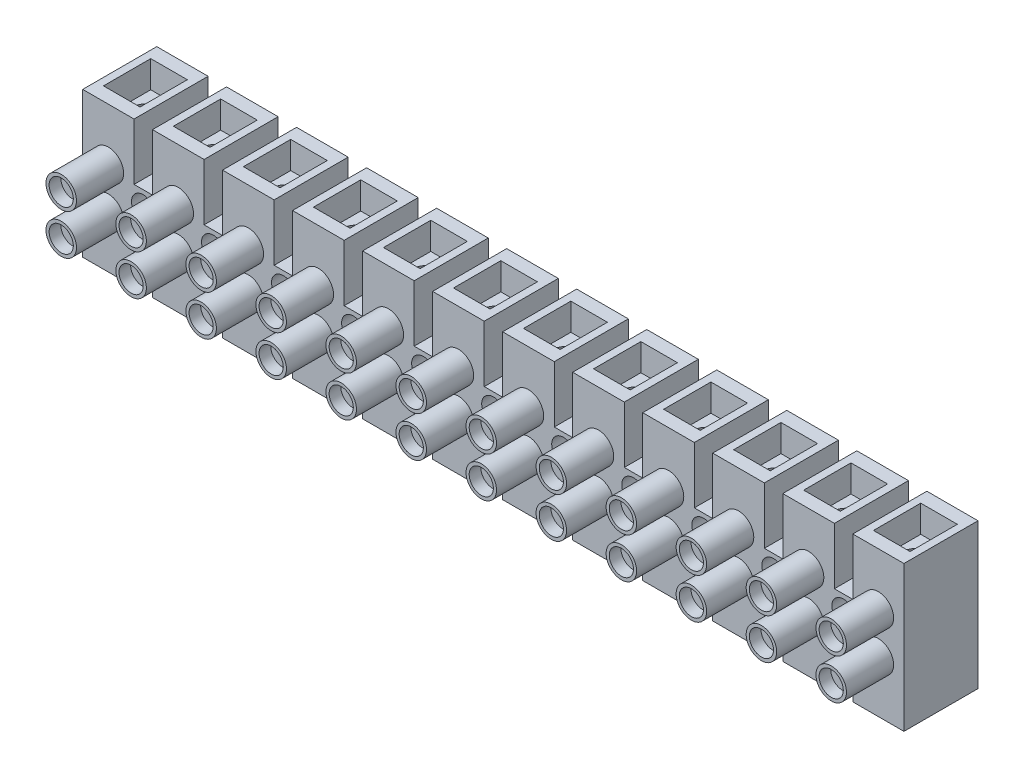
SolidWorks part; units mm, degrees
ref_plane "Front Plane" through (0, 0, 0) normal (0, 0, 1) x (1, 0, 0)
ref_plane "Top Plane" through (0, 0, 0) normal (0, 1, 0) x (1, 0, 0)
ref_plane "Right Plane" through (0, 0, 0) normal (1, 0, 0) x (0, 0, -1)
sketch "Sketch1" plane through (0, 0, 0) normal (0, 0, 1) x (1, 0, 0)
  line L1 (0, 16.9545) -> (95.758, 16.9545)
  line L2 (0, 16.9545) -> (0, 0)
  line L3 (0, 0) -> (95.758, 0)
  line L4 (95.758, 16.9545) -> (95.758, 0)
  dimension "D1" = 95.758
  dimension "D2" = 16.9545
extrude "Boss-Extrude1" add sketch "Sketch1" along normal blind 8.636
sketch "Sketch2" plane through (0, 0, 8.636) normal (0, 0, 1) x (1, 0, 0)
  line L0 (0, 8.4773) -> (95.758, 8.4773) construction
  line L1 (0, 16.9545) -> (0, 0) construction
  line L2 (95.758, 0) -> (95.758, 16.9545) construction
  line L3 (22.3202, 16.9545) -> (24.4666, 16.9545)
  line L4 (5.988, 16.9545) -> (8.1343, 16.9545)
  line L5 (5.988, 16.9545) -> (5.9881, 10.3505)
  line L6 (5.9881, 10.3505) -> (8.1343, 10.3505)
  line L7 (8.1343, 16.9545) -> (8.1343, 10.3505)
  line L8 (14.1542, 16.9545) -> (16.3005, 16.9545)
  line L9 (95.758, 16.9545) -> (0, 16.9545) construction
  line L10 (7.0612, 16.9545) -> (7.0612, 0) construction
  line L11 (15.2273, 16.9545) -> (15.2273, 0) construction
  line L12 (23.3934, 16.9545) -> (23.3934, 0) construction
  line L13 (31.5595, 16.9545) -> (31.5595, 0) construction
  line L14 (39.7256, 16.9545) -> (39.7256, 0) construction
  line L15 (47.8917, 16.9545) -> (47.8917, 0) construction
  line L16 (56.0578, 16.9545) -> (56.0578, 0) construction
  line L17 (64.2239, 16.9545) -> (64.2239, 0) construction
  line L18 (72.39, 16.9545) -> (72.39, 0) construction
  line L19 (88.7222, 16.9545) -> (88.7222, 0) construction
  line L20 (80.5561, 16.9545) -> (80.5561, 0) construction
  line L21 (0, 0) -> (95.758, 0) construction
  line L22 (14.1542, 16.9545) -> (14.1542, 10.3505)
  line L23 (14.1542, 10.3505) -> (16.3005, 10.3505)
  line L24 (16.3005, 16.9545) -> (16.3005, 10.3505)
  line L25 (22.3202, 16.9545) -> (22.3203, 10.3505)
  line L26 (22.3203, 10.3505) -> (24.4666, 10.3505)
  line L27 (24.4666, 16.9545) -> (24.4666, 10.3505)
  line L28 (30.4864, 16.9545) -> (32.6326, 16.9545)
  line L29 (30.4864, 16.9545) -> (30.4864, 10.3505)
  line L30 (30.4864, 10.3505) -> (32.6327, 10.3505)
  line L31 (32.6326, 16.9545) -> (32.6327, 10.3505)
  line L32 (38.6525, 16.9545) -> (40.7988, 16.9545)
  line L33 (38.6525, 16.9545) -> (38.6525, 10.3505)
  line L34 (38.6525, 10.3505) -> (40.7988, 10.3505)
  line L35 (40.7988, 16.9545) -> (40.7988, 10.3505)
  line L36 (46.8186, 16.9545) -> (48.9648, 16.9545)
  line L37 (46.8186, 16.9545) -> (46.8186, 10.3505)
  line L38 (46.8186, 10.3505) -> (48.9649, 10.3505)
  line L39 (48.9648, 16.9545) -> (48.9649, 10.3505)
  line L40 (54.9847, 16.9545) -> (57.131, 16.9545)
  line L41 (54.9847, 16.9545) -> (54.9847, 10.3505)
  line L42 (54.9847, 10.3505) -> (57.131, 10.3505)
  line L43 (57.131, 16.9545) -> (57.131, 10.3505)
  line L44 (63.1508, 16.9545) -> (65.2971, 16.9545)
  line L45 (63.1508, 16.9545) -> (63.1508, 10.3505)
  line L46 (63.1508, 10.3505) -> (65.2971, 10.3505)
  line L47 (65.2971, 16.9545) -> (65.2971, 10.3505)
  line L48 (71.3169, 16.9545) -> (73.4631, 16.9545)
  line L49 (71.3169, 16.9545) -> (71.3169, 10.3505)
  line L50 (71.3169, 10.3505) -> (73.4631, 10.3505)
  line L51 (73.4631, 16.9545) -> (73.4631, 10.3505)
  line L52 (79.483, 16.9545) -> (81.6292, 16.9545)
  line L53 (79.483, 16.9545) -> (79.483, 10.3505)
  line L54 (79.483, 10.3505) -> (81.6293, 10.3505)
  line L55 (81.6292, 16.9545) -> (81.6293, 10.3505)
  line L56 (87.6491, 16.9545) -> (89.7953, 16.9545)
  line L57 (87.6491, 16.9545) -> (87.6491, 10.3505)
  line L58 (87.6491, 10.3505) -> (89.7953, 10.3505)
  line L59 (89.7953, 16.9545) -> (89.7953, 10.3505)
  line L60 (5.988, 6.604) -> (8.1343, 6.604)
  line L61 (5.988, 6.604) -> (5.9881, 0)
  line L62 (5.9881, 0) -> (8.1343, 0)
  line L63 (8.1343, 6.604) -> (8.1343, 0)
  line L64 (14.1542, 6.604) -> (16.3005, 6.604)
  line L65 (14.1542, 6.604) -> (14.1542, 0)
  line L66 (14.1542, 0) -> (16.3005, 0)
  line L67 (16.3005, 6.604) -> (16.3005, 0)
  line L68 (22.3203, 6.604) -> (24.4666, 6.604)
  line L69 (22.3203, 6.604) -> (22.3203, 0)
  line L70 (22.3203, 0) -> (24.4666, 0)
  line L71 (24.4666, 6.604) -> (24.4666, 0)
  line L72 (30.4864, 6.604) -> (32.6326, 6.604)
  line L73 (30.4864, 6.604) -> (30.4864, 0)
  line L74 (30.4864, 0) -> (32.6326, 0)
  line L75 (32.6326, 6.604) -> (32.6326, 0)
  line L76 (38.6525, 6.604) -> (40.7987, 6.604)
  line L77 (38.6525, 6.604) -> (38.6525, 0)
  line L78 (38.6525, 0) -> (40.7987, 0)
  line L79 (40.7987, 6.604) -> (40.7987, 0)
  line L80 (48.9649, 6.604) -> (46.8186, 6.604)
  line L81 (48.9649, 6.604) -> (48.9649, 0)
  line L82 (48.9649, 0) -> (46.8186, 0)
  line L83 (46.8186, 6.604) -> (46.8186, 0)
  line L84 (57.131, 6.604) -> (54.9847, 6.604)
  line L85 (57.131, 6.604) -> (57.131, 0)
  line L86 (57.131, 0) -> (54.9847, 0)
  line L87 (54.9847, 6.604) -> (54.9847, 0)
  line L88 (63.1508, 6.604) -> (65.2971, 6.604)
  line L89 (63.1508, 6.604) -> (63.1508, 0)
  line L90 (63.1508, 0) -> (65.2971, 0)
  line L91 (65.2971, 6.604) -> (65.2971, 0)
  line L92 (71.3169, 6.604) -> (73.4631, 6.604)
  line L93 (71.3169, 6.604) -> (71.3169, 0)
  line L94 (71.3169, 0) -> (73.4632, 0)
  line L95 (73.4631, 6.604) -> (73.4632, 0)
  line L96 (79.483, 6.604) -> (81.6292, 6.604)
  line L97 (79.483, 6.604) -> (79.483, 0)
  line L98 (79.483, 0) -> (81.6293, 0)
  line L99 (81.6292, 6.604) -> (81.6293, 0)
  line L100 (89.7953, 6.604) -> (87.6491, 6.604)
  line L101 (89.7953, 6.604) -> (89.7953, 0)
  line L102 (89.7953, 0) -> (87.6491, 0)
  line L103 (87.6491, 6.604) -> (87.6491, 0)
  circle A0 centre (15.2273, 8.4773) radius 1.3716
  circle A1 centre (23.3934, 8.4773) radius 1.3716
  circle A2 centre (31.5595, 8.4773) radius 1.3716
  circle A3 centre (39.7256, 8.4773) radius 1.3716
  circle A4 centre (47.8917, 8.4773) radius 1.3716
  circle A5 centre (56.0578, 8.4773) radius 1.3716
  circle A6 centre (7.0612, 8.4773) radius 1.3716
  circle A7 centre (64.2239, 8.4773) radius 1.3716
  circle A8 centre (72.39, 8.4773) radius 1.3716
  circle A9 centre (80.5561, 8.4773) radius 1.3716
  circle A10 centre (88.7222, 8.4773) radius 1.3716
  dimension "D1" = 2.7432
  dimension "D2" = 7.0358
  dimension "D3" = 8.1661
  dimension "D4" = 8.1661
  dimension "D5" = 8.1661
  dimension "D6" = 8.1661
  dimension "D7" = 8.1661
  dimension "D8" = 8.1661
  dimension "D9" = 8.1661
  dimension "D10" = 8.1661
  dimension "D11" = 8.1661
  dimension "D12" = 8.1661
  dimension "D13" = 2.1463
  dimension "D14" = 6.604
extrude "Cut-Extrude2" cut sketch "Sketch2" against normal up to surface (8.636 mm away) up to face at (47.879, 8.4773, 0)
sketch "Sketch3" plane through (0, 0, 8.636) normal (0, 0, 1) x (1, 0, 0)
  line L0 (0, 6.1087) -> (95.758, 6.1087) construction
  line L1 (79.483, 16.9545) -> (73.4631, 16.9545) construction
  line L2 (0, 16.9545) -> (0, 0) construction
  line L3 (95.758, 0) -> (95.758, 16.9545) construction
  line L4 (95.758, 10.8458) -> (0, 10.8458) construction
  line L5 (47.879, 10.8458) -> (47.879, 6.1087) construction
  line L6 (95.758, 8.4773) -> (0, 8.4773) construction
  line L7 (92.7767, 16.9545) -> (92.7767, 0) construction
  line L8 (84.6392, 16.9545) -> (84.6392, 0) construction
  line L9 (76.4731, 16.9545) -> (76.4731, 0) construction
  line L10 (68.307, 16.9545) -> (68.307, 0) construction
  line L11 (60.1409, 16.9545) -> (60.1409, 0) construction
  line L12 (51.9748, 16.9545) -> (51.9748, 0) construction
  line L13 (43.8087, 16.9545) -> (43.8087, 0) construction
  line L14 (35.6425, 16.9545) -> (35.6425, 0) construction
  line L15 (27.4765, 16.9545) -> (27.4765, 0) construction
  line L16 (19.3103, 16.9545) -> (19.3104, 0) construction
  line L17 (11.1442, 16.9545) -> (11.1443, 0) construction
  line L18 (2.994, 16.9545) -> (2.994, 0) construction
  line L19 (5.988, 16.9545) -> (0, 16.9545) construction
  line L20 (0, 0) -> (5.9881, 0) construction
  line L21 (14.1542, 16.9545) -> (8.1343, 16.9545) construction
  line L22 (8.1343, 0) -> (14.1542, 0) construction
  line L23 (22.3202, 16.9545) -> (16.3005, 16.9545) construction
  line L24 (16.3005, 0) -> (22.3203, 0) construction
  line L25 (30.4864, 16.9545) -> (24.4666, 16.9545) construction
  line L26 (24.4666, 0) -> (30.4864, 0) construction
  line L27 (38.6525, 16.9545) -> (32.6326, 16.9545) construction
  line L28 (32.6326, 0) -> (38.6525, 0) construction
  line L29 (46.8186, 16.9545) -> (40.7988, 16.9545) construction
  line L30 (40.7987, 0) -> (46.8186, 0) construction
  line L31 (54.9847, 16.9545) -> (48.9648, 16.9545) construction
  line L32 (48.9649, 0) -> (54.9847, 0) construction
  line L33 (63.1508, 16.9545) -> (57.131, 16.9545) construction
  line L34 (57.131, 0) -> (63.1508, 0) construction
  line L35 (71.3169, 16.9545) -> (65.2971, 16.9545) construction
  line L36 (65.2971, 0) -> (71.3169, 0) construction
  line L37 (73.4632, 0) -> (79.483, 0) construction
  line L38 (87.6491, 16.9545) -> (81.6292, 16.9545) construction
  line L39 (81.6293, 0) -> (87.6491, 0) construction
  line L40 (95.758, 16.9545) -> (89.7953, 16.9545) construction
  line L41 (89.7953, 0) -> (95.758, 0) construction
  circle A0 centre (92.7767, 6.1087) radius 1.778
  circle A1 centre (11.1443, 10.8458) radius 1.778
  circle A2 centre (19.3103, 10.8458) radius 1.778
  circle A3 centre (27.4765, 10.8458) radius 1.778
  circle A4 centre (35.6425, 10.8458) radius 1.778
  circle A5 centre (43.8087, 10.8458) radius 1.778
  circle A6 centre (51.9748, 10.8458) radius 1.778
  circle A7 centre (60.1409, 10.8458) radius 1.778
  circle A8 centre (68.307, 10.8458) radius 1.778
  circle A9 centre (76.4731, 10.8458) radius 1.778
  circle A10 centre (84.6392, 10.8458) radius 1.778
  circle A11 centre (92.7767, 10.8458) radius 1.778
  circle A12 centre (2.994, 10.8458) radius 1.778
  circle A13 centre (2.994, 6.1087) radius 1.778
  circle A14 centre (11.1443, 6.1087) radius 1.778
  circle A15 centre (19.3103, 6.1087) radius 1.778
  circle A16 centre (27.4765, 6.1087) radius 1.778
  circle A17 centre (35.6426, 6.1087) radius 1.778
  circle A18 centre (43.8087, 6.1087) radius 1.778
  circle A19 centre (51.9748, 6.1087) radius 1.778
  circle A20 centre (60.1409, 6.1087) radius 1.778
  circle A21 centre (68.307, 6.1087) radius 1.778
  circle A22 centre (76.4731, 6.1087) radius 1.778
  circle A23 centre (84.6392, 6.1087) radius 1.778
  point P16 (47.879, 8.4773)
  dimension "D1" = 3.556
  dimension "D2" = 4.7371
extrude "Boss-Extrude2" add sketch "Sketch3" along normal blind 5.4991
sketch "Sketch4" plane through (0, 0, 14.1351) normal (0, 0, 1) x (1, 0, 0)
  circle A0 centre (11.1443, 6.1087) radius 1.4097
  circle A1 centre (19.3103, 6.1087) radius 1.4097
  circle A2 centre (27.4765, 6.1087) radius 1.4097
  circle A3 centre (35.6426, 6.1087) radius 1.4097
  circle A4 centre (43.8087, 6.1087) radius 1.4097
  circle A5 centre (51.9748, 6.1087) radius 1.4097
  circle A6 centre (60.1409, 6.1087) radius 1.4097
  circle A7 centre (68.307, 6.1087) radius 1.4097
  circle A8 centre (76.4731, 6.1087) radius 1.4097
  circle A9 centre (84.6392, 6.1087) radius 1.4097
  circle A10 centre (92.7767, 6.1087) radius 1.4097
  circle A11 centre (92.7767, 10.8458) radius 1.4097
  circle A12 centre (84.6392, 10.8458) radius 1.4097
  circle A13 centre (76.4731, 10.8458) radius 1.4097
  circle A14 centre (68.307, 10.8458) radius 1.4097
  circle A15 centre (60.1409, 10.8458) radius 1.4097
  circle A16 centre (51.9748, 10.8458) radius 1.4097
  circle A17 centre (43.8087, 10.8458) radius 1.4097
  circle A18 centre (35.6425, 10.8458) radius 1.4097
  circle A19 centre (27.4765, 10.8458) radius 1.4097
  circle A20 centre (19.3103, 10.8458) radius 1.4097
  circle A21 centre (11.1443, 10.8458) radius 1.4097
  circle A22 centre (2.994, 10.8458) radius 1.4097
  circle A23 centre (2.994, 6.1087) radius 1.4097
  circle A26 centre (92.7767, 10.8458) radius 1.778 construction
  circle A27 centre (84.6392, 10.8458) radius 1.778 construction
  circle A28 centre (76.4731, 10.8458) radius 1.778 construction
  circle A29 centre (68.307, 10.8458) radius 1.778 construction
  circle A30 centre (60.1409, 10.8458) radius 1.778 construction
  circle A31 centre (51.9748, 10.8458) radius 1.778 construction
  circle A32 centre (43.8087, 10.8458) radius 1.778 construction
  circle A33 centre (35.6425, 10.8458) radius 1.778 construction
  circle A34 centre (27.4765, 10.8458) radius 1.778 construction
  circle A35 centre (19.3103, 10.8458) radius 1.778 construction
  circle A36 centre (11.1443, 10.8458) radius 1.778 construction
  circle A37 centre (2.994, 10.8458) radius 1.778 construction
  circle A38 centre (2.994, 6.1087) radius 1.778 construction
  circle A39 centre (11.1443, 6.1087) radius 1.778 construction
  circle A40 centre (19.3103, 6.1087) radius 1.778 construction
  circle A41 centre (27.4765, 6.1087) radius 1.778 construction
  circle A42 centre (35.6426, 6.1087) radius 1.778 construction
  circle A43 centre (43.8087, 6.1087) radius 1.778 construction
  circle A44 centre (51.9748, 6.1087) radius 1.778 construction
  circle A45 centre (60.1409, 6.1087) radius 1.778 construction
  circle A46 centre (68.307, 6.1087) radius 1.778 construction
  circle A47 centre (76.4731, 6.1087) radius 1.778 construction
  circle A48 centre (84.6392, 6.1087) radius 1.778 construction
  circle A49 centre (92.7767, 6.1087) radius 1.778 construction
  dimension "D1" = 2.8194
extrude "Cut-Extrude3" cut sketch "Sketch4" against normal blind 1.3589
sketch "Sketch5" plane through (0, 0, 0) normal (0, -1, 0) x (1, 0, 0)
  line L0 (27.4765, 8.636) -> (27.4765, 0) construction
  line L1 (35.6425, 8.636) -> (35.6425, 0) construction
  line L2 (43.8087, 8.636) -> (43.8087, 0) construction
  line L3 (51.9748, 8.636) -> (51.9748, 0) construction
  line L4 (60.1409, 8.636) -> (60.1409, 0) construction
  line L5 (68.307, 8.636) -> (68.307, 0) construction
  line L6 (76.4731, 8.636) -> (76.4731, 0) construction
  line L7 (84.6392, 8.636) -> (84.6392, 0) construction
  line L8 (92.7767, 8.636) -> (92.7767, 0) construction
  line L9 (19.3104, 8.636) -> (19.3104, 0) construction
  line L10 (11.1443, 8.636) -> (11.1443, 0) construction
  line L11 (2.994, 8.636) -> (2.994, 0) construction
  line L12 (0, 8.636) -> (5.9881, 8.636) construction
  line L13 (0, 0) -> (5.9881, 0) construction
  line L14 (8.1343, 8.636) -> (14.1542, 8.636) construction
  line L15 (8.1343, 0) -> (14.1542, 0) construction
  line L16 (16.3005, 8.636) -> (22.3203, 8.636) construction
  line L17 (16.3005, 0) -> (22.3203, 0) construction
  line L18 (24.4666, 8.636) -> (30.4864, 8.636) construction
  line L19 (24.4666, 0) -> (30.4864, 0) construction
  line L20 (32.6326, 8.636) -> (38.6525, 8.636) construction
  line L21 (40.7987, 8.636) -> (46.8186, 8.636) construction
  line L22 (48.9649, 8.636) -> (54.9847, 8.636) construction
  line L23 (57.131, 8.636) -> (63.1508, 8.636) construction
  line L24 (65.2971, 8.636) -> (71.3169, 8.636) construction
  line L25 (73.4632, 8.636) -> (79.483, 8.636) construction
  line L26 (81.6293, 8.636) -> (87.6491, 8.636) construction
  line L27 (89.7953, 8.636) -> (95.758, 8.636) construction
  line L28 (32.6326, 0) -> (38.6525, 0) construction
  line L29 (40.7987, 0) -> (46.8186, 0) construction
  line L30 (48.9649, 0) -> (54.9847, 0) construction
  line L31 (57.131, 0) -> (63.1508, 0) construction
  line L32 (65.2971, 0) -> (71.3169, 0) construction
  line L33 (73.4632, 0) -> (79.483, 0) construction
  line L34 (81.6293, 0) -> (87.6491, 0) construction
  line L35 (89.7953, 0) -> (95.758, 0) construction
  line L36 (9.0107, 7.0739) -> (13.2779, 7.0739)
  line L37 (0.8604, 7.0739) -> (5.1276, 7.0739)
  line L38 (0.8604, 7.0739) -> (0.8604, 1.5621)
  line L39 (0.8604, 1.5621) -> (5.1276, 1.5621)
  line L40 (5.1276, 7.0739) -> (5.1276, 1.5621)
  line L41 (9.0107, 7.0739) -> (9.0107, 1.5621)
  line L42 (9.0107, 1.5621) -> (13.2779, 1.5621)
  line L43 (13.2779, 7.0739) -> (13.2779, 1.5621)
  line L44 (25.3429, 7.0739) -> (29.6101, 7.0739)
  line L45 (25.3429, 7.0739) -> (25.3429, 1.5621)
  line L46 (25.3429, 1.5621) -> (29.6101, 1.5621)
  line L47 (29.6101, 7.0739) -> (29.6101, 1.5621)
  line L48 (33.5089, 7.0739) -> (37.7761, 7.0739)
  line L49 (33.5089, 7.0739) -> (33.5089, 1.5621)
  line L50 (33.5089, 1.5621) -> (37.7761, 1.5621)
  line L51 (37.7761, 7.0739) -> (37.7761, 1.5621)
  line L52 (41.6751, 7.0739) -> (45.9423, 7.0739)
  line L53 (41.6751, 7.0739) -> (41.6751, 1.5621)
  line L54 (41.6751, 1.5621) -> (45.9423, 1.5621)
  line L55 (45.9423, 7.0739) -> (45.9423, 1.5621)
  line L56 (17.1768, 7.0739) -> (21.444, 7.0739)
  line L57 (17.1768, 7.0739) -> (17.1768, 1.5621)
  line L58 (17.1768, 1.5621) -> (21.444, 1.5621)
  line L59 (21.444, 7.0739) -> (21.444, 1.5621)
  line L60 (66.1734, 7.0739) -> (70.4406, 7.0739)
  line L61 (66.1734, 7.0739) -> (66.1734, 1.5621)
  line L62 (66.1734, 1.5621) -> (70.4406, 1.5621)
  line L63 (70.4406, 7.0739) -> (70.4406, 1.5621)
  line L64 (74.3395, 7.0739) -> (78.6067, 7.0739)
  line L65 (74.3395, 7.0739) -> (74.3395, 1.5621)
  line L66 (74.3395, 1.5621) -> (78.6067, 1.5621)
  line L67 (78.6067, 7.0739) -> (78.6067, 1.5621)
  line L68 (82.5056, 7.0739) -> (86.7728, 7.0739)
  line L69 (82.5056, 7.0739) -> (82.5056, 1.5621)
  line L70 (82.5056, 1.5621) -> (86.7728, 1.5621)
  line L71 (86.7728, 7.0739) -> (86.7728, 1.5621)
  line L72 (49.8411, 7.0739) -> (54.1084, 7.0739)
  line L73 (49.8411, 7.0739) -> (49.8411, 1.5621)
  line L74 (49.8411, 1.5621) -> (54.1084, 1.5621)
  line L75 (54.1084, 7.0739) -> (54.1084, 1.5621)
  line L76 (90.6431, 7.0739) -> (94.9103, 7.0739)
  line L77 (90.6431, 7.0739) -> (90.6431, 1.5621)
  line L78 (90.6431, 1.5621) -> (94.9103, 1.5621)
  line L79 (94.9103, 7.0739) -> (94.9103, 1.5621)
  line L80 (58.0073, 7.0739) -> (62.2745, 7.0739)
  line L81 (58.0073, 7.0739) -> (58.0073, 1.5621)
  line L82 (58.0073, 1.5621) -> (62.2745, 1.5621)
  line L83 (62.2745, 7.0739) -> (62.2745, 1.5621)
  line L92 (0, 4.318) -> (5.9881, 4.318) construction
  line L93 (8.1344, 4.318) -> (14.1542, 4.318) construction
  line L94 (16.3005, 4.318) -> (22.3203, 4.318) construction
  line L95 (24.4666, 4.318) -> (30.4864, 4.318) construction
  line L96 (32.6326, 4.318) -> (38.6525, 4.318) construction
  line L97 (40.7987, 4.318) -> (46.8186, 4.318) construction
  line L98 (48.9649, 4.318) -> (54.9847, 4.318) construction
  line L99 (57.131, 4.318) -> (63.1508, 4.318) construction
  line L100 (65.2971, 4.318) -> (71.3169, 4.318) construction
  line L101 (73.4631, 4.318) -> (79.483, 4.318) construction
  line L102 (81.6293, 4.318) -> (87.6491, 4.318) construction
  line L103 (89.7953, 4.318) -> (95.758, 4.318) construction
  line L104 (0, 8.636) -> (0, 0) construction
  line L105 (5.9881, 0) -> (5.9881, 8.636) construction
  line L106 (8.1344, 0) -> (8.1344, 8.636) construction
  line L107 (14.1542, 0) -> (14.1542, 8.636) construction
  line L108 (16.3005, 0) -> (16.3005, 8.636) construction
  line L109 (22.3203, 0) -> (22.3203, 8.636) construction
  line L110 (24.4666, 0) -> (24.4666, 8.636) construction
  line L111 (30.4864, 0) -> (30.4864, 8.636) construction
  line L112 (32.6326, 0) -> (32.6326, 8.636) construction
  line L113 (38.6525, 0) -> (38.6525, 8.636) construction
  line L114 (40.7987, 0) -> (40.7987, 8.636) construction
  line L115 (46.8186, 0) -> (46.8186, 8.636) construction
  line L116 (48.9649, 0) -> (48.9649, 8.636) construction
  line L117 (54.9847, 0) -> (54.9847, 8.636) construction
  line L118 (57.131, 0) -> (57.131, 8.636) construction
  line L119 (63.1508, 0) -> (63.1508, 8.636) construction
  line L120 (65.2971, 0) -> (65.2971, 8.636) construction
  line L121 (71.3169, 0) -> (71.3169, 8.636) construction
  line L122 (73.4631, 0) -> (73.4631, 8.636) construction
  line L123 (79.483, 0) -> (79.483, 8.636) construction
  line L124 (81.6293, 0) -> (81.6293, 8.636) construction
  line L125 (87.6491, 0) -> (87.6491, 8.636) construction
  line L126 (95.758, 8.636) -> (95.758, 0) construction
  line L127 (89.7953, 0) -> (89.7953, 8.636) construction
  point P80 (11.1442, 7.0739)
  point P81 (13.2779, 4.318)
  point P87 (27.4765, 7.0739)
  point P89 (29.6101, 4.318)
  point P94 (35.6425, 7.0739)
  point P96 (37.7761, 4.318)
  point P101 (43.8087, 7.0739)
  point P103 (45.9423, 4.318)
  point P108 (19.3104, 7.0739)
  point P110 (21.444, 4.318)
  point P115 (68.307, 7.0739)
  point P117 (70.4406, 4.318)
  point P122 (76.4731, 7.0739)
  point P124 (78.6067, 4.318)
  point P128 (2.994, 7.0739)
  point P202 (5.1276, 4.318)
  point P205 (84.6392, 7.0739)
  point P207 (86.7728, 4.318)
  point P212 (51.9748, 7.0739)
  point P214 (54.1084, 4.318)
  point P219 (92.7767, 7.0739)
  point P221 (94.9103, 4.318)
  point P226 (60.1409, 7.0739)
  point P228 (62.2745, 4.318)
  dimension "D1" = 5.5118
  dimension "D2" = 4.2672
extrude "Cut-Extrude4" cut sketch "Sketch5" against normal blind 3.1496
sketch "Sketch6" plane through (0, 16.9545, 0) normal (0, 1, 0) x (1, 0, 0)
  line L0 (8.1343, -4.318) -> (14.1541, -4.318) construction
  line L1 (16.3005, -4.318) -> (22.3203, -4.318) construction
  line L2 (24.4666, -4.318) -> (30.4864, -4.318) construction
  line L3 (32.6326, -4.318) -> (38.6525, -4.318) construction
  line L4 (40.7988, -4.318) -> (46.8186, -4.318) construction
  line L5 (48.9648, -4.318) -> (54.9847, -4.318) construction
  line L6 (57.131, -4.318) -> (63.1508, -4.318) construction
  line L7 (65.2971, -4.318) -> (71.3169, -4.318) construction
  line L8 (73.4631, -4.318) -> (79.483, -4.318) construction
  line L9 (81.6292, -4.318) -> (87.6491, -4.318) construction
  line L10 (89.7953, -4.318) -> (95.758, -4.318) construction
  line L11 (2.994, 0) -> (2.994, -8.636) construction
  line L12 (14.1541, 0) -> (14.1541, -8.636) construction
  line L13 (0.8604, -1.5621) -> (5.1276, -1.5621)
  line L14 (0.8604, -1.5621) -> (0.8604, -7.0739)
  line L15 (0.8604, -7.0739) -> (5.1276, -7.0739)
  line L16 (5.1276, -1.5621) -> (5.1276, -7.0739)
  line L17 (8.1343, 0) -> (8.1343, -8.636) construction
  line L18 (16.3005, 0) -> (16.3005, -8.636) construction
  line L19 (22.3203, 0) -> (22.3203, -8.636) construction
  line L20 (24.4666, 0) -> (24.4666, -8.636) construction
  line L21 (30.4864, 0) -> (30.4864, -8.636) construction
  line L22 (32.6326, 0) -> (32.6326, -8.636) construction
  line L23 (38.6525, 0) -> (38.6525, -8.636) construction
  line L24 (40.7988, 0) -> (40.7988, -8.636) construction
  line L25 (46.8186, 0) -> (46.8186, -8.636) construction
  line L26 (48.9648, 0) -> (48.9648, -8.636) construction
  line L27 (54.9847, 0) -> (54.9847, -8.636) construction
  line L28 (57.131, 0) -> (57.131, -8.636) construction
  line L29 (63.1508, 0) -> (63.1508, -8.636) construction
  line L30 (65.2971, 0) -> (65.2971, -8.636) construction
  line L31 (71.3169, 0) -> (71.3169, -8.636) construction
  line L32 (25.3429, -1.5621) -> (29.6101, -1.5621)
  line L33 (73.4631, 0) -> (73.4631, -8.636) construction
  line L34 (79.483, 0) -> (79.483, -8.636) construction
  line L35 (81.6292, 0) -> (81.6292, -8.636) construction
  line L36 (87.6491, 0) -> (87.6491, -8.636) construction
  line L37 (89.7953, 0) -> (89.7953, -8.636) construction
  line L38 (95.758, -8.636) -> (95.758, 0) construction
  line L39 (11.1442, 0) -> (11.1442, -8.636) construction
  line L40 (19.3103, 0) -> (19.3103, -8.636) construction
  line L41 (27.4764, 0) -> (27.4764, -8.636) construction
  line L42 (35.6425, 0) -> (35.6425, -8.636) construction
  line L43 (43.8087, 0) -> (43.8087, -8.636) construction
  line L44 (51.9747, 0) -> (51.9747, -8.636) construction
  line L45 (68.3069, 0) -> (68.3069, -8.636) construction
  line L46 (84.6392, 0) -> (84.6392, -8.636) construction
  line L47 (92.7767, 0) -> (92.7767, -8.636) construction
  line L48 (76.4731, 0) -> (76.4731, -8.636) construction
  line L49 (60.1409, 0) -> (60.1409, -8.636) construction
  line L50 (14.1541, -8.636) -> (8.1343, -8.636) construction
  line L51 (14.1541, 0) -> (8.1343, 0) construction
  line L52 (22.3202, -8.636) -> (16.3005, -8.636) construction
  line L53 (30.4864, -8.636) -> (24.4666, -8.636) construction
  line L54 (38.6525, -8.636) -> (32.6326, -8.636) construction
  line L55 (46.8186, -8.636) -> (40.7988, -8.636) construction
  line L56 (54.9847, -8.636) -> (48.9648, -8.636) construction
  line L57 (63.1508, -8.636) -> (57.131, -8.636) construction
  line L58 (71.3169, -8.636) -> (65.2971, -8.636) construction
  line L59 (79.483, -8.636) -> (73.4631, -8.636) construction
  line L60 (0, -4.318) -> (5.988, -4.318) construction
  line L61 (87.6491, -8.636) -> (81.6292, -8.636) construction
  line L62 (95.758, -8.636) -> (89.7953, -8.636) construction
  line L63 (25.3429, -1.5621) -> (25.3429, -7.0739)
  line L64 (17.1767, -1.5621) -> (21.444, -1.5621)
  line L65 (17.1767, -1.5621) -> (17.1767, -7.0739)
  line L66 (17.1767, -7.0739) -> (21.444, -7.0739)
  line L67 (21.444, -1.5621) -> (21.444, -7.0739)
  line L68 (25.3429, -7.0739) -> (29.6101, -7.0739)
  line L69 (29.6101, -1.5621) -> (29.6101, -7.0739)
  line L70 (9.0106, -1.5621) -> (13.2778, -1.5621)
  line L71 (9.0106, -1.5621) -> (9.0106, -7.0739)
  line L72 (9.0106, -7.0739) -> (13.2778, -7.0739)
  line L73 (13.2778, -1.5621) -> (13.2778, -7.0739)
  line L74 (5.988, -8.636) -> (0, -8.636) construction
  line L75 (5.988, 0) -> (0, 0) construction
  line L76 (0, -8.636) -> (0, 0) construction
  line L77 (5.9881, 0) -> (5.9881, -8.636) construction
  line L78 (74.3395, -1.5621) -> (78.6067, -1.5621)
  line L79 (74.3395, -1.5621) -> (74.3395, -7.0739)
  line L80 (74.3395, -7.0739) -> (78.6067, -7.0739)
  line L81 (78.6067, -1.5621) -> (78.6067, -7.0739)
  line L82 (33.5089, -1.5621) -> (37.7761, -1.5621)
  line L83 (33.5089, -1.5621) -> (33.5089, -7.0739)
  line L84 (33.5089, -7.0739) -> (37.7761, -7.0739)
  line L85 (37.7761, -1.5621) -> (37.7761, -7.0739)
  line L86 (41.6751, -1.5621) -> (45.9423, -1.5621)
  line L87 (41.6751, -1.5621) -> (41.6751, -7.0739)
  line L88 (41.6751, -7.0739) -> (45.9423, -7.0739)
  line L89 (45.9423, -1.5621) -> (45.9423, -7.0739)
  line L90 (49.8411, -1.5621) -> (54.1084, -1.5621)
  line L91 (49.8411, -1.5621) -> (49.8411, -7.0739)
  line L92 (49.8411, -7.0739) -> (54.1084, -7.0739)
  line L93 (54.1084, -1.5621) -> (54.1084, -7.0739)
  line L94 (66.1733, -1.5621) -> (70.4406, -1.5621)
  line L95 (66.1733, -1.5621) -> (66.1733, -7.0739)
  line L96 (66.1733, -7.0739) -> (70.4406, -7.0739)
  line L97 (70.4406, -1.5621) -> (70.4406, -7.0739)
  line L98 (90.6431, -1.5621) -> (94.9103, -1.5621)
  line L99 (90.6431, -1.5621) -> (90.6431, -7.0739)
  line L100 (90.6431, -7.0739) -> (94.9103, -7.0739)
  line L101 (94.9103, -1.5621) -> (94.9103, -7.0739)
  line L102 (82.5055, -1.5621) -> (86.7728, -1.5621)
  line L103 (82.5055, -1.5621) -> (82.5055, -7.0739)
  line L104 (82.5055, -7.0739) -> (86.7728, -7.0739)
  line L105 (86.7728, -1.5621) -> (86.7728, -7.0739)
  line L106 (58.0073, -1.5621) -> (62.2745, -1.5621)
  line L107 (58.0073, -1.5621) -> (58.0073, -7.0739)
  line L108 (58.0073, -7.0739) -> (62.2745, -7.0739)
  line L109 (62.2745, -1.5621) -> (62.2745, -7.0739)
  point P73 (2.994, -1.5621)
  point P98 (5.1276, -4.318)
  point P136 (19.3103, -1.5621)
  point P139 (21.4439, -4.318)
  point P140 (27.4765, -1.5621)
  point P141 (29.6101, -4.318)
  point P146 (11.1442, -1.5621)
  point P147 (13.2779, -4.318)
  point P152 (76.4731, -1.5621)
  point P153 (78.6067, -4.318)
  point P158 (35.6425, -1.5621)
  point P159 (37.7762, -4.318)
  point P164 (43.8087, -1.5621)
  point P165 (45.9423, -4.318)
  point P170 (51.9748, -1.5621)
  point P171 (54.1084, -4.318)
  point P176 (68.307, -1.5621)
  point P177 (70.4406, -4.318)
  point P182 (92.7767, -1.5621)
  point P183 (94.9103, -4.318)
  point P188 (84.6392, -1.5621)
  point P189 (86.7728, -4.318)
  point P194 (60.1409, -1.5621)
  point P195 (62.2745, -4.318)
  dimension "D1" = 5.5118
  dimension "D2" = 4.2672
extrude "Cut-Extrude5" cut sketch "Sketch6" against normal blind 3.1496
sketch "Sketch7" plane through (0, 3.1496, 0) normal (0, -1, 0) x (-1, 0, 0)
  line L0 (-2.994, -7.0739) -> (-2.994, -1.5621) construction
  line L1 (-11.1443, -7.0739) -> (-11.1443, -1.5621) construction
  line L2 (-19.3103, -7.0739) -> (-19.3104, -1.5621) construction
  line L3 (-27.4765, -7.0739) -> (-27.4765, -1.5621) construction
  line L4 (-35.6425, -7.0739) -> (-35.6425, -1.5621) construction
  line L5 (-43.8087, -7.0739) -> (-43.8087, -1.5621) construction
  line L6 (-51.9748, -7.0739) -> (-51.9748, -1.5621) construction
  line L7 (-60.1409, -7.0739) -> (-60.1409, -1.5621) construction
  line L8 (-68.307, -7.0739) -> (-68.307, -1.5621) construction
  line L9 (-76.4731, -7.0739) -> (-76.4731, -1.5621) construction
  line L10 (-84.6392, -7.0739) -> (-84.6392, -1.5621) construction
  line L11 (-92.7767, -7.0739) -> (-92.7767, -1.5621) construction
  line L12 (-0.8604, -1.5621) -> (-5.1276, -1.5621) construction
  line L13 (-5.1276, -7.0739) -> (-0.8604, -7.0739) construction
  line L14 (-9.0107, -1.5621) -> (-13.2779, -1.5621) construction
  line L15 (-13.2779, -7.0739) -> (-9.0107, -7.0739) construction
  line L16 (-21.444, -7.0739) -> (-17.1768, -7.0739) construction
  line L17 (-17.1768, -1.5621) -> (-21.444, -1.5621) construction
  line L18 (-25.3429, -1.5621) -> (-29.6101, -1.5621) construction
  line L19 (-29.6101, -7.0739) -> (-25.3429, -7.0739) construction
  line L20 (-37.7761, -7.0739) -> (-33.5089, -7.0739) construction
  line L21 (-33.5089, -1.5621) -> (-37.7761, -1.5621) construction
  line L22 (-41.6751, -1.5621) -> (-45.9423, -1.5621) construction
  line L23 (-45.9423, -7.0739) -> (-41.6751, -7.0739) construction
  line L24 (-54.1084, -7.0739) -> (-49.8411, -7.0739) construction
  line L25 (-49.8411, -1.5621) -> (-54.1084, -1.5621) construction
  line L26 (-58.0073, -1.5621) -> (-62.2745, -1.5621) construction
  line L27 (-62.2745, -7.0739) -> (-58.0073, -7.0739) construction
  line L28 (-70.4406, -7.0739) -> (-66.1734, -7.0739) construction
  line L29 (-66.1734, -1.5621) -> (-70.4406, -1.5621) construction
  line L30 (-74.3395, -1.5621) -> (-78.6067, -1.5621) construction
  line L31 (-78.6067, -7.0739) -> (-74.3395, -7.0739) construction
  line L32 (-86.7728, -7.0739) -> (-82.5056, -7.0739) construction
  line L33 (-82.5056, -1.5621) -> (-86.7728, -1.5621) construction
  line L34 (-94.9103, -7.0739) -> (-90.6431, -7.0739) construction
  line L35 (-90.6431, -1.5621) -> (-94.9103, -1.5621) construction
  circle A0 centre (-92.7767, -4.318) radius 1.4351
  circle A1 centre (-2.994, -4.318) radius 1.4351
  circle A2 centre (-11.1443, -4.318) radius 1.4351
  circle A3 centre (-19.3104, -4.318) radius 1.4351
  circle A4 centre (-27.4765, -4.318) radius 1.4351
  circle A5 centre (-35.6425, -4.318) radius 1.4351
  circle A6 centre (-43.8087, -4.318) radius 1.4351
  circle A7 centre (-51.9747, -4.318) radius 1.4351
  circle A8 centre (-60.1409, -4.318) radius 1.4351
  circle A9 centre (-68.307, -4.318) radius 1.4351
  circle A10 centre (-76.4731, -4.318) radius 1.4351
  circle A11 centre (-84.6392, -4.318) radius 1.4351
  dimension "D1" = 2.8702
extrude "Cut-Extrude6" cut sketch "Sketch7" against normal up to surface (10.6553 mm away) up to face at (27.4765, 13.8049, 4.318)
